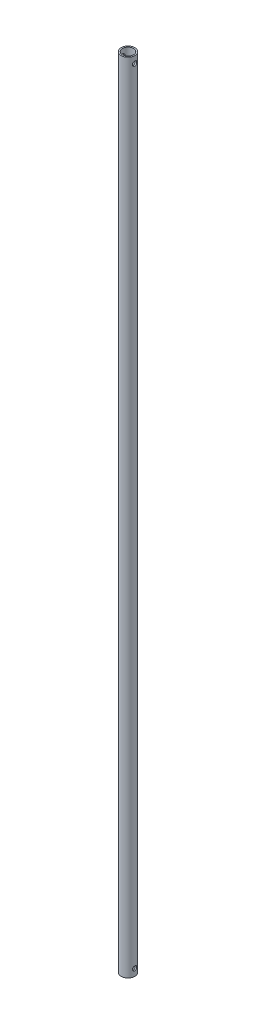
SolidWorks part; units mm, degrees
material "Toray T700"
ref_plane "Front" through (0, 0, 0) normal (0, 0, 1) x (1, 0, 0)
ref_plane "Top" through (0, 0, 0) normal (0, 1, 0) x (1, 0, 0)
ref_plane "Right" through (0, 0, 0) normal (1, 0, 0) x (0, 0, -1)
sketch "Sketch1" plane through (0, 0, 0) normal (0, 1, 0) x (1, 0, 0)
  line L5 (4.7969, 0) -> (-5.97, 0) construction
  circle A0 centre (0, 0) radius 5
  circle A1 centre (0, 0) radius 4
  dimension "D1" = 10
  dimension "D2" = 8
extrude "Boss-Extrude1" add sketch "Sketch1" along normal mid plane 579
ref_axis "Axis1" through (0, 289.5, 0) along (0, -1, 0)
ref_plane "Plane1" through (-5, 0, 0) normal (-1, 0, 0) x (0, 0, 1)
hole_wizard "M3 Clearance Hole1" positions "Sketch3" profile "Sketch2" hole size "M3" standard "DIN" end condition through all
sketch "Sketch3" plane through (-5, 0, 0) normal (-1, 0, 0) x (0, 0, 1)
  line L0 (-4, -289.5) -> (4, -289.5) construction
  line L1 (0, -50) -> (0, 50) construction
  point P0 (0, -284.5)
  dimension "D1" = 5
sketch "Sketch2" plane through (-5, -284.5, 0) normal (0, 1, 0) x (0, 0, 1)
  line L0 (0, 0) -> (0, 10)
  line L1 (0, 10) -> (1.6, 10)
  line L2 (1.6, 10) -> (1.6, 0)
  line L5 (1.6, 0) -> (0, 0)
  line L11 (0, -6.35) -> (0, 107.95) construction
  dimension "Thru Hole Dia." = 3.2
  dimension "Thru Hole Depth" = 10
ref_plane "Plane2" through (0, 0, 0) normal (0, 1, 0) x (1, 0, 0)
mirror "Mirror1" about plane through (0, 0, 0) normal (0, 1, 0) of "M3 Clearance Hole1"
